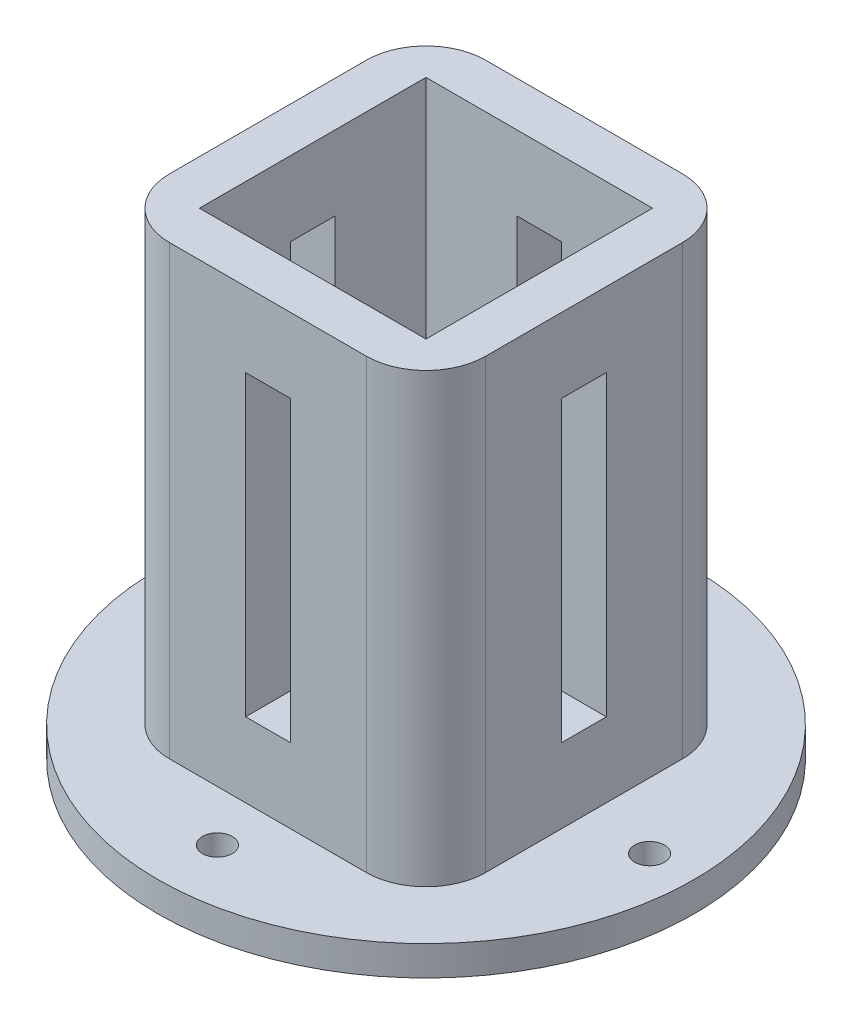
SolidWorks part; units mm, degrees
ref_plane "Front Plane" through (0, 0, 0) normal (0, 0, 1) x (1, 0, 0)
ref_plane "Top Plane" through (0, 0, 0) normal (0, 1, 0) x (1, 0, 0)
ref_plane "Right Plane" through (0, 0, 0) normal (1, 0, 0) x (0, 0, -1)
sketch "Sketch1" plane through (0, 0, 0) normal (0, 1, 0) x (1, 0, 0)
  line L1 (-7.6, -7.6) -> (7.6, -7.6)
  line L2 (-7.6, -7.6) -> (-7.6, 7.6)
  line L3 (-7.6, 7.6) -> (7.6, 7.6)
  line L4 (7.6, -7.6) -> (7.6, 7.6)
  line L5 (-7.6, -7.6) -> (7.6, 7.6) construction
  line L6 (-7.6, 7.6) -> (7.6, -7.6) construction
  line L7 (-10.6, -10.6) -> (10.6, -10.6)
  line L8 (-10.6, -10.6) -> (-10.6, 10.6)
  line L9 (-10.6, 10.6) -> (10.6, 10.6)
  line L10 (10.6, -10.6) -> (10.6, 10.6)
  line L11 (-10.6, -10.6) -> (10.6, 10.6) construction
  line L12 (-10.6, 10.6) -> (10.6, -10.6) construction
  point P0 (0, 0)
  point P6 (0, 0)
  dimension "D1" = 15.2
  dimension "D2" = 15.2
  dimension "D3" = 3
  dimension "D4" = 3
extrude "Boss-Extrude1" add sketch "Sketch1" along normal blind 30
sketch "Sketch2" plane through (0, 0, 0) normal (0, -1, 0) x (1, 0, 0)
  line L1 (-10.6, -10.6) -> (10.6, -10.6)
  line L2 (-10.6, -10.6) -> (-10.6, 10.6)
  line L3 (-10.6, 10.6) -> (10.6, 10.6)
  line L4 (10.6, -10.6) -> (10.6, 10.6)
  line L5 (-10.6, -10.6) -> (10.6, 10.6) construction
  line L6 (-10.6, 10.6) -> (10.6, -10.6) construction
  point P0 (0, 0)
fillet "Fillet1" radius 4 4 edges at (-10.6, 15, -10.6) (10.6, 15, -10.6) (10.6, 15, 10.6) (-10.6, 15, 10.6)
sketch "Sketch3" plane through (0, 0, 0) normal (0, -1, 0) x (1, 0, 0)
  circle A1 centre (0, 0) radius 18
  dimension "D1" = 36
extrude "Boss-Extrude2" add sketch "Sketch3" along normal blind 2
sketch "Sketch4" plane through (0, 0, 0) normal (0, 1, 0) x (1, 0, 0)
  circle A0 centre (0, 0) radius 1.5
  dimension "D1" = 3
extrude "Cut-Extrude2" cut sketch "Sketch4" against normal up to next
sketch "Sketch5" plane through (0, 0, -10.6) normal (0, 0, -1) x (-1, 0, 0)
  line L0 (0, 30) -> (0, 0) construction
  line L5 (-6.6, 30) -> (6.6, 30) construction
  line L6 (-6.6, 0) -> (6.6, 0) construction
  line L7 (-1.5, 5) -> (1.5, 5)
  line L8 (-1.5, 5) -> (-1.5, 25)
  line L9 (-1.5, 25) -> (1.5, 25)
  line L10 (1.5, 5) -> (1.5, 25)
  line L11 (-1.5, 5) -> (1.5, 25) construction
  line L12 (-1.5, 25) -> (1.5, 5) construction
  point P0 (0, 15)
  dimension "D1" = 3
  dimension "D2" = 20
  dimension "D3" = 5
extrude "Cut-Extrude3" cut sketch "Sketch5" against normal through all
sketch "Sketch6" plane through (10.6, 0, 0) normal (1, 0, 0) x (0, 0, -1)
  line L0 (0, 30) -> (0, 0) construction
  line L1 (-6.6, 30) -> (6.6, 30) construction
  line L3 (-1.5, 5) -> (1.5, 5)
  line L4 (-1.5, 5) -> (-1.5, 25)
  line L5 (-1.5, 25) -> (1.5, 25)
  line L6 (1.5, 5) -> (1.5, 25)
  line L7 (-1.5, 5) -> (1.5, 25) construction
  line L8 (-1.5, 25) -> (1.5, 5) construction
  point P5 (0, 15)
  dimension "D1" = 3
  dimension "D2" = 20
extrude "Cut-Extrude4" cut sketch "Sketch6" against normal through all
sketch "Sketch7" plane through (0, -2, 0) normal (0, -1, 0) x (-1, 0, 0)
  line L0 (0, 0) -> (0, 14) construction
  line L1 (0, -18) -> (0, 0) construction
  line L4 (0, 0) -> (-12, 0) construction
  line L5 (0, 0) -> (14, 0) construction
  circle A0 centre (0, 0) radius 18 construction
  circle A1 centre (14, 0) radius 1
  circle A2 centre (-15, 0) radius 1
  circle A3 centre (0, 14) radius 1
  circle A4 centre (0, -14) radius 1
  dimension "D3" = 2
  dimension "D4" = 2
  dimension "D1" = 12
  dimension "D2" = 14
  dimension "D5" = 14
extrude "Cut-Extrude5" cut sketch "Sketch7" against normal blind 2
fillet "Fillet4" radius 1 1 edges at (0, 0, 1.5) conic radius 10
fillet "Fillet5" radius 0.2 1 edges at (0, -2, -1.5)
